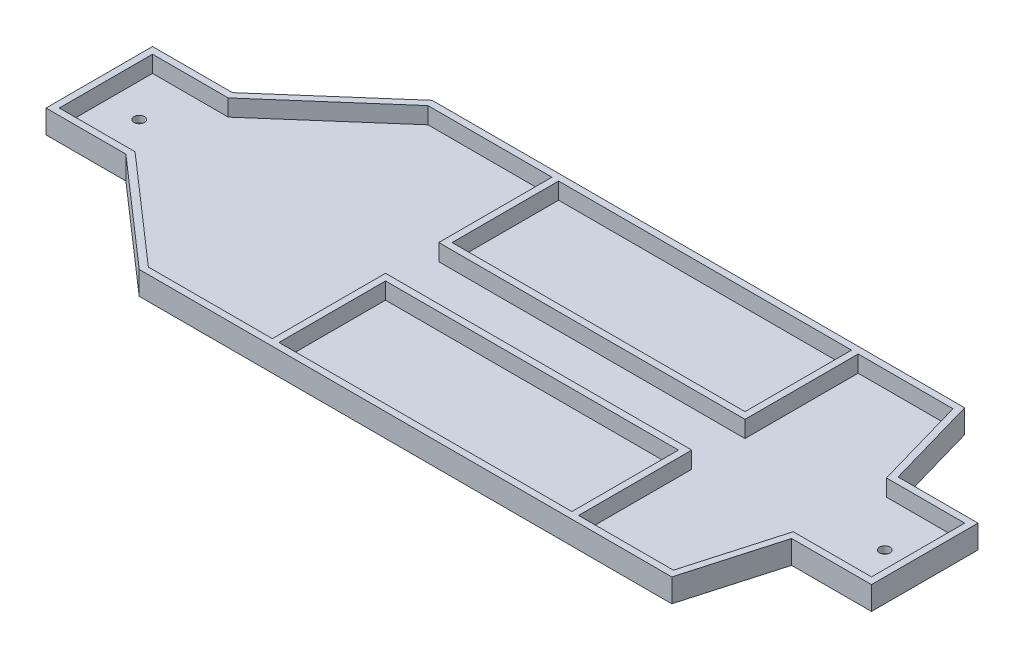
SolidWorks part; units mm, degrees
ref_plane "Front Plane" through (0, 0, 0) normal (0, 0, 1) x (1, 0, 0)
ref_plane "Top Plane" through (0, 0, 0) normal (0, 1, 0) x (1, 0, 0)
ref_plane "Right Plane" through (0, 0, 0) normal (1, 0, 0) x (0, 0, -1)
sketch "Sketch1" plane through (0, 0, 0) normal (0, 1, 0) x (1, 0, 0)
  line L0 (-127, 69.85) -> (-177.8, 25.4)
  line L1 (-127, 69.85) -> (127, 69.85)
  line L2 (-127, 69.85) -> (-127, -69.85) construction
  line L3 (-127, -69.85) -> (127, -69.85)
  line L4 (127, 69.85) -> (127, -69.85) construction
  line L5 (-127, 69.85) -> (127, -69.85) construction
  line L6 (-127, -69.85) -> (127, 69.85) construction
  line L7 (-177.8, 25.4) -> (-215.9, 25.4)
  line L8 (-215.9, 25.4) -> (-215.9, -25.4)
  line L9 (-215.9, -25.4) -> (-177.8, -25.4)
  line L10 (-177.8, -25.4) -> (-127, -69.85)
  line L11 (127, -69.85) -> (139.7, -25.4)
  line L12 (139.7, -25.4) -> (177.8, -25.4)
  line L13 (177.8, -25.4) -> (177.8, 25.4)
  line L14 (177.8, 25.4) -> (139.7, 25.4)
  line L15 (139.7, 25.4) -> (127, 69.85)
  line L16 (-215.9, 25.4) -> (-177.8, -25.4) construction
  line L17 (139.7, 25.4) -> (177.8, -25.4) construction
  line L18 (-125.807, 66.675) -> (-176.607, 22.225)
  line L19 (-63.5, -15.875) -> (76.2, -15.875)
  line L20 (-63.5, -15.875) -> (-63.5, -66.675)
  line L21 (-63.5, -66.675) -> (76.2, -66.675)
  line L22 (76.2, -15.875) -> (76.2, -66.675)
  line L23 (-63.5, -15.875) -> (76.2, -66.675) construction
  line L24 (-63.5, -66.675) -> (76.2, -15.875) construction
  line L25 (-63.5, 66.675) -> (76.2, 66.675)
  line L26 (-63.5, 66.675) -> (-63.5, 15.875)
  line L27 (-63.5, 15.875) -> (76.2, 15.875)
  line L28 (76.2, 66.675) -> (76.2, 15.875)
  line L29 (-63.5, 66.675) -> (76.2, 15.875) construction
  line L30 (-63.5, 15.875) -> (76.2, 66.675) construction
  line L31 (-176.607, 22.225) -> (-212.725, 22.225)
  line L32 (-212.725, 22.225) -> (-212.725, -22.225)
  line L33 (-212.725, -22.225) -> (-176.607, -22.225)
  line L34 (-176.607, -22.225) -> (-125.807, -66.675)
  line L35 (-125.807, -66.675) -> (124.6051, -66.675)
  line L36 (124.6051, -66.675) -> (137.3051, -22.225)
  line L37 (137.3051, -22.225) -> (174.625, -22.225)
  line L38 (174.625, -22.225) -> (174.625, 22.225)
  line L39 (174.625, 22.225) -> (137.3051, 22.225)
  line L40 (137.3051, 22.225) -> (124.6051, 66.675)
  line L41 (-125.807, 66.675) -> (124.6051, 66.675)
  line L42 (-66.675, 69.85) -> (-66.675, 12.7)
  line L43 (-66.675, 12.7) -> (79.375, 12.7)
  line L44 (79.375, 69.85) -> (79.375, 12.7)
  line L45 (-66.675, 69.85) -> (79.375, 69.85)
  line L46 (-66.675, -12.7) -> (79.375, -12.7)
  line L47 (79.375, -12.7) -> (79.375, -69.85)
  line L48 (-66.675, -69.85) -> (79.375, -69.85)
  line L49 (-66.675, -12.7) -> (-66.675, -69.85)
  circle A0 centre (-196.85, 0) radius 2.4892
  circle A1 centre (158.75, 0) radius 2.4892
  point P0 (0, 0)
  point P18 (6.35, -41.275)
  point P23 (6.35, 41.275)
  dimension "D2" = 4.9784
  dimension "D1" = 254
  dimension "D3" = 355.6
  dimension "D4" = 139.7
  dimension "D5" = 50.8
  dimension "D6" = 3.175
  dimension "D7" = 3.175
  dimension "D8" = 139.7
  dimension "D9" = 50.8
  dimension "D10" = 50.8
  dimension "D11" = 50.8
  dimension "D12" = 50.8
  dimension "D13" = 88.9
  dimension "D14" = 3.175
  dimension "D15" = 3.175
extrude "Boss-Extrude1" add sketch "Sketch1" along normal blind 3.175 contours L49 L46 L47 L35 L36 L37 L38 L39 L40 L41 L44 L43 L42 L18 L31 L32 L33 L34 A1 A0 | L28 L25 L26 L27 | L22 L19 L20 L21 | L49 L35 L34 L33 L32 L31 L18 L41 L42 L1 L0 L7 L8 L9 L10 L3 | L46 L49 L35 L20 L19 L22 L47 | L35 L49 L3 L47 L21 | L35 L47 L3 L11 L12 L13 L14 L15 L1 L44 L41 L40 L39 L38 L37 L36 | L44 L1 L42 L41 L25 | L44 L41 L28 L27 L26 L42 L43 region at (-96.8375, 0, -67.8059) region at (6.35, 0, -68.2625) region at (103.1875, 0, -68.1411) region at (-26.0534, 0, 0) region at (-65.0875, 0, -65.118) region at (6.35, 0, -41.275) region at (6.35, 0, 68.2625) region at (-65.118, 0, 39.6875) region at (6.35, 0, 41.275)
extrude "Boss-Extrude2" add sketch "Sketch1<3>" along normal blind 11.1125 contours L49 L35 L34 L33 L32 L31 L18 L41 L42 L1 L0 L7 L8 L9 L10 L3 | L46 L49 L35 L20 L19 L22 L47 | L35 L49 L3 L47 L21 | L44 L1 L42 L41 L25 | L44 L41 L28 L27 L26 L42 L43 | L35 L47 L3 L11 L12 L13 L14 L15 L1 L44 L41 L40 L39 L38 L37 L36 region at (-96.8375, 0, -67.8059) region at (6.35, 0, -68.2625) region at (103.1875, 0, -68.1411) region at (-65.0875, 0, -65.118) region at (6.35, 0, 68.2625) region at (-65.118, 0, 39.6875)
sketch "Sketch1<3>" plane through (0, 0, 0) normal (0, 1, 0) x (1, 0, 0) same geometry as "Sketch1"
equation "\"D7@Sketch1\"=\"D6@Sketch1\""
